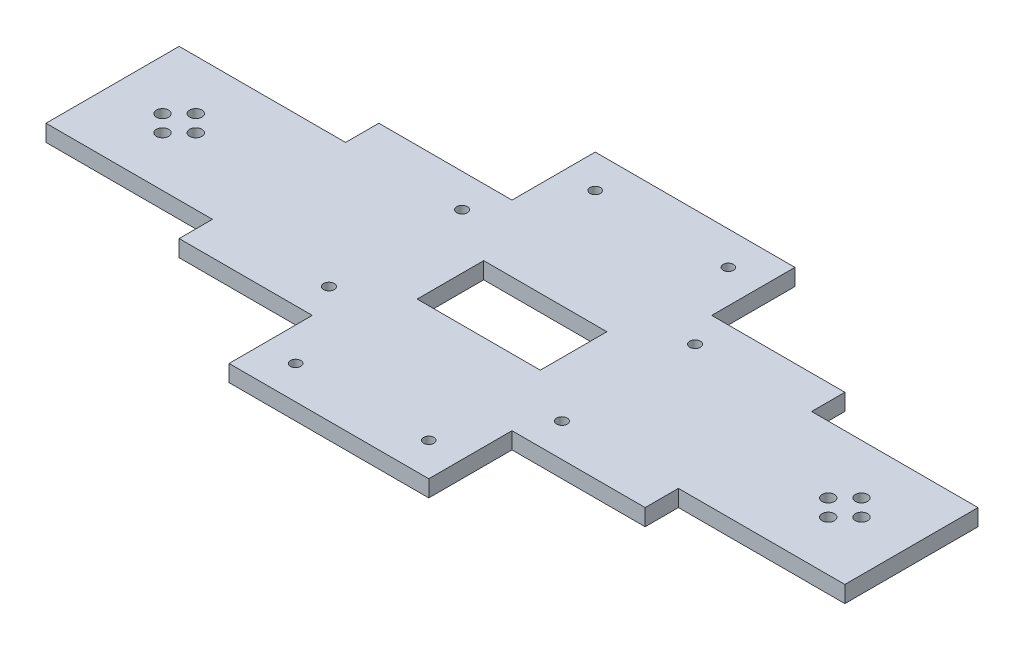
SolidWorks part; units mm, degrees
ref_plane "Front Plane" through (0, 0, 0) normal (0, 0, 1) x (1, 0, 0)
ref_plane "Top Plane" through (0, 0, 0) normal (0, 1, 0) x (1, 0, 0)
ref_plane "Right Plane" through (0, 0, 0) normal (1, 0, 0) x (0, 0, -1)
sketch "Sketch1" plane through (0, 0, 0) normal (0, 1, 0) x (1, 0, 0)
  line L0 (0, 50) -> (0, -43.3333) construction
  line L1 (120, 0) -> (100, 0) construction
  line L2 (-70, 30) -> (70, 30)
  line L3 (0, 30) -> (0, -30)
  line L4 (-70, -30) -> (70, -30)
  line L5 (70, 30) -> (70, -30)
  line L6 (70, 20) -> (120, 20)
  line L7 (70, 20) -> (70, -20)
  line L8 (70, -20) -> (120, -20)
  line L9 (120, 20) -> (120, -20)
  line L10 (120, 20) -> (70, 20) construction
  line L11 (100, 0) -> (120, 0) construction
  line L13 (120, 0) -> (100, 0) construction
  line L14 (100, 0) -> (100, 15) construction
  line L15 (-100, 0) -> (-100, 15) construction
  line L16 (-120, 0) -> (-100, 0) construction
  line L17 (-100, 0) -> (-120, 0) construction
  line L18 (-120, 20) -> (-70, 20) construction
  line L19 (-120, 0) -> (-100, 0) construction
  line L20 (-120, 20) -> (-120, -20)
  line L21 (-70, -20) -> (-120, -20)
  line L22 (-70, 20) -> (-70, -20)
  line L23 (-70, 20) -> (-120, 20)
  line L24 (-70, 30) -> (-70, -30)
  line L25 (-18.5, 10) -> (-18.5, -10)
  line L26 (-18.5, 10) -> (18.5, 10)
  line L27 (0, 10) -> (0, -10)
  line L28 (-18.5, -10) -> (18.5, -10)
  line L29 (18.5, 10) -> (18.5, -10)
  line L31 (0, 30) -> (32.0822, 30)
  line L32 (0, 30) -> (0, 55.2592)
  line L33 (0, 55.2592) -> (32.0822, 55.2592)
  line L34 (32.0822, 30) -> (32.0822, 55.2592)
  line L35 (0, -30) -> (32.0822, -30)
  line L36 (0, -30) -> (0, -49.982)
  line L37 (0, -49.982) -> (32.0822, -49.982)
  line L38 (32.0822, -30) -> (32.0822, -49.982)
  circle A0 centre (100, 5) radius 1.85
  circle A1 centre (105, 0) radius 1.85
  circle A2 centre (100, -5) radius 1.85
  circle A3 centre (95, 0) radius 1.85
  circle A4 centre (-95, 0) radius 1.85
  circle A5 centre (-100, -5) radius 1.85
  circle A6 centre (-105, 0) radius 1.85
  circle A7 centre (-100, 5) radius 1.85
  circle A8 centre (35, 20) radius 1.6
  circle A9 centre (35, -20) radius 1.6
  circle A10 centre (-35, -20) radius 1.6
  circle A11 centre (-35, 20) radius 1.6
  circle A12 centre (17.0822, -43) radius 1.55
  point P25 (100, 0)
  point P26 (70, -15)
  point P43 (-70, -15)
  point P44 (-100, 0)
  dimension "D8" = 3.7
  dimension "D9" = 5
  dimension "D11" = 5
  dimension "D12" = 5
  dimension "D13" = 30
  dimension "D14" = 10
  dimension "D7" = 35
  dimension "D17" = 20
  dimension "D18" = 3.2
  dimension "D19" = 3.2
  dimension "D20" = 40
  dimension "D21" = 3.1
  dimension "D22" = 15
  dimension "D23" = 13
  dimension "D1" = 30
  dimension "D2" = 30
  dimension "D3" = 10
  dimension "D4" = 10
  dimension "D5" = 70
  dimension "D6" = 50
  dimension "D15" = 10
  dimension "D16" = 18.5
  dimension "D10" = 4
extrude "Boss-Extrude1" add sketch "Sketch1" along normal blind 5 contours L5 L2 L3 L4 | L9 L6 L5 L8 A3 A2 A1 A0 | L22 L23 L20 L21 A6 A4 A5 A7 | L2 L24 L22 L4 L3 region at (-37.4981, 0, 0) region at (37.4981, 0, 0) region at (-70.6403, 0, 0) region at (95, 0, -19.3597)
sketch "Sketch2" plane through (0, 5, 0) normal (0, 1, 0) x (1, 0, 0)
  line L0 (-70, 30) -> (70, 30) construction
  line L1 (-30, 30) -> (30, 30)
  line L2 (0, 30) -> (0, 55)
  line L3 (-30, 55) -> (30, 55)
  line L4 (30, 30) -> (30, 55)
  line L5 (-70, -30) -> (70, -30) construction
  line L6 (-30, -30) -> (30, -30)
  line L7 (0, -30) -> (0, -55)
  line L8 (-30, -55) -> (30, -55)
  line L9 (30, -30) -> (30, -55)
  line L10 (0, 0) -> (0, -19.3557) construction
  line L11 (-30, -30) -> (-30, -55)
  line L12 (-30, 30) -> (-30, 55)
  line L13 (0, 0) -> (30, 0) construction
  circle A0 centre (20, -45) radius 1.55
  circle A2 centre (20, 45) radius 1.55
  circle A3 centre (-20, -45) radius 1.55
  circle A4 centre (-20, 45) radius 1.55
  line M6 (-70, -30) -> (70, -30)
  line M12 (70, 30) -> (-70, 30)
  dimension "D5" = 3.1
  dimension "D6" = 10
  dimension "D7" = 10
  dimension "D1" = 25
  dimension "D2" = 25
  dimension "D3" = 30
  dimension "D4" = 30
extrude "Boss-Extrude2" add sketch "Sketch2" against normal blind 5 contours L4 L3 L2 M12 | L12 L1 L2 L3 | L11 L8 L7 A3 M6 | L9 L6 L7 L8 A0 region at (-14.9492, 5, -42.4746) region at (14.9492, 5, -42.4746) region at (-14.9492, 5, 42.4746) region at (14.9492, 5, 42.4746)
